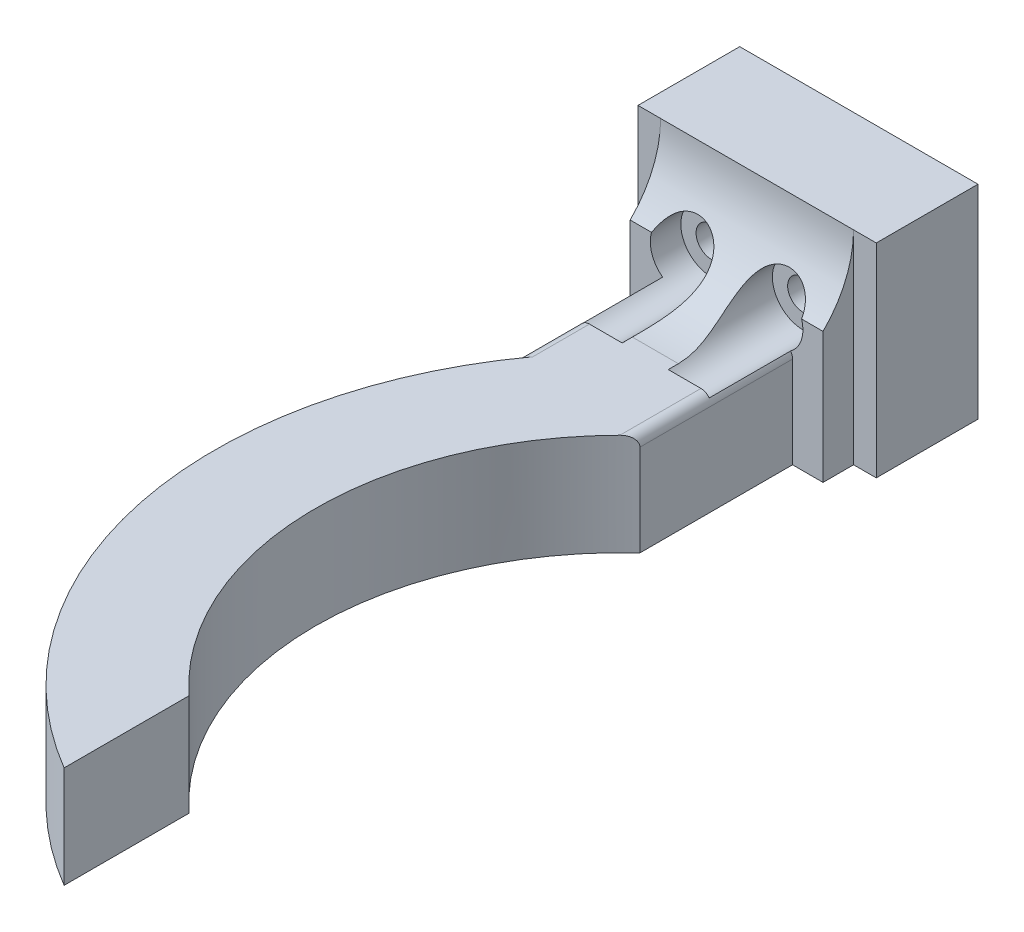
SolidWorks part; units mm, degrees
ref_plane "Front Plane" through (0, 0, 0) normal (0, 0, 1) x (1, 0, 0)
ref_plane "Top Plane" through (0, 0, 0) normal (0, 1, 0) x (1, 0, 0)
ref_plane "Right Plane" through (0, 0, 0) normal (1, 0, 0) x (0, 0, -1)
sketch "Sketch1" plane through (0, 0, 0) normal (0, 0, 1) x (1, 0, 0)
  line L0 (-15.1944, -0.9494) -> (3.7656, -0.9494)
  line L1 (-15.1944, 9.0506) -> (3.7656, 9.0506)
  line L2 (-15.1944, 9.0506) -> (-15.1944, -10.9494)
  line L3 (-15.1944, -10.9494) -> (3.7656, -10.9494)
  line L4 (3.7656, 9.0506) -> (3.7656, -10.9494)
  line L5 (-15.1944, -5.9494) -> (3.7656, -5.9494)
  dimension "D1" = 18.96
  dimension "D2" = 20
extrude "Boss-Extrude1" add sketch "Sketch1" against normal blind 10 contours L4 L1 L2 | L2 L5 L4 | L5 L2 L3 L4 region at (-5.7144, 4.0506, 0) region at (-5.7144, -3.4494, 0) region at (-5.7144, -8.4494, 0)
extrude "Boss-Extrude3" add sketch "Sketch1<4>" along normal blind 3 contours L2 L5 L4 L0 | L5 L2 L3 L4 region at (-5.7144, -3.4494, 0) region at (-5.7144, -8.4494, 0)
sketch "Sketch1<4>" plane through (0, 0, 0) normal (0, 0, 1) x (1, 0, 0) same geometry as "Sketch1"
ref_plane "Plane3" through (0, 0, 3) normal (0, 0, 1) x (1, 0, 0)
sketch "Sketch3" plane through (0, 0, 3) normal (0, 0, 1) x (1, 0, 0)
  line L0 (-15.1944, -0.9494) -> (3.7656, -0.9494)
  line L1 (3.7656, -0.9494) -> (3.7656, -10.9494)
  line L2 (3.7656, -10.9494) -> (-15.1944, -10.9494)
  line L3 (-15.1944, -10.9494) -> (-15.1944, -0.9494)
  line L4 (0.7656, -0.9494) -> (0.7656, -10.9494)
  line L5 (-12.1944, -0.9494) -> (-12.1944, -10.9494)
  dimension "D1" = 3
  dimension "D2" = 3
extrude "Boss-Extrude4" add sketch "Sketch3" along normal blind 15 contours L0 L5 L2 L4 region at (-5.7144, -5.9494, 3)
sketch "Sketch4" plane through (0, -0.9494, 0) normal (0, 1, 0) x (1, 0, 0)
  line L0 (0.7656, -18) -> (0.7656, -5.7152)
  line L1 (0.7656, -18) -> (0.7656, -3) construction
  line L2 (0.7656, -62.3111) -> (0.7656, -74.5959)
  arc A1 (0.7656, -18) -> (0.7656, -62.3111) centre (21.1092, -40.1555) ccw
  arc A2 (0.7656, -5.7152) -> (0.7656, -74.5959) centre (21.1092, -40.1555) ccw
extrude "Boss-Extrude5" add sketch "Sketch4" against normal blind 10
ref_plane "Plane5" through (0, 0, -10) normal (0, 0, -1) x (-1, 0, 0)
sketch "Sketch6" plane through (0, 0, -10) normal (0, 0, -1) x (-1, 0, 0)
  line L0 (15.1944, 9.0506) -> (-3.7656, 9.0506) construction
  line L1 (17.4244, 9.0506) -> (-5.9956, 9.0506)
  line L2 (17.4244, 9.0506) -> (17.4244, -10.9494)
  line L3 (17.4244, -10.9494) -> (-5.9956, -10.9494)
  line L4 (-5.9956, 9.0506) -> (-5.9956, -10.9494)
  line L5 (-3.7656, 9.0506) -> (-3.7656, -10.9494) construction
  circle A0 centre (10.2144, 1.0506) radius 1.5
  circle A1 centre (1.2144, 1.0506) radius 1.5
  circle A2 centre (10.2144, 1.0506) radius 3
  circle A3 centre (1.2144, 1.0506) radius 3
  dimension "D4" = 9
  dimension "D1" = 20
  dimension "D2" = 23.42
  dimension "D3" = 2.23
  dimension "D5" = 7.21
  dimension "D6" = 8
  dimension "D7" = 8
extrude "Boss-Extrude6" add sketch "Sketch6" against normal blind 10 contours A3 | A2 | L2 L3 L4 L1
fillet "Fillet1" radius 10 1 edges at (-5.7144, -0.9494, 0)
extrude "Cut-Extrude2" cut sketch "Sketch6<5>" against normal blind 21 contours A2 | A3
sketch "Sketch6<5>" plane through (0, 0, -10) normal (0, 0, -1) x (-1, 0, 0) same geometry as "Sketch6"
extrude "Boss-Extrude7" add sketch "Sketch6<6>" against normal blind 10 contours A0 | A2 | A1 | A3
sketch "Sketch6<6>" plane through (0, 0, -10) normal (0, 0, -1) x (-1, 0, 0) same geometry as "Sketch6"
fillet "Fillet2" radius 1 2 edges at (-12.1944, -0.9494, 14.5) (0.7656, -0.9494, 14.5)
